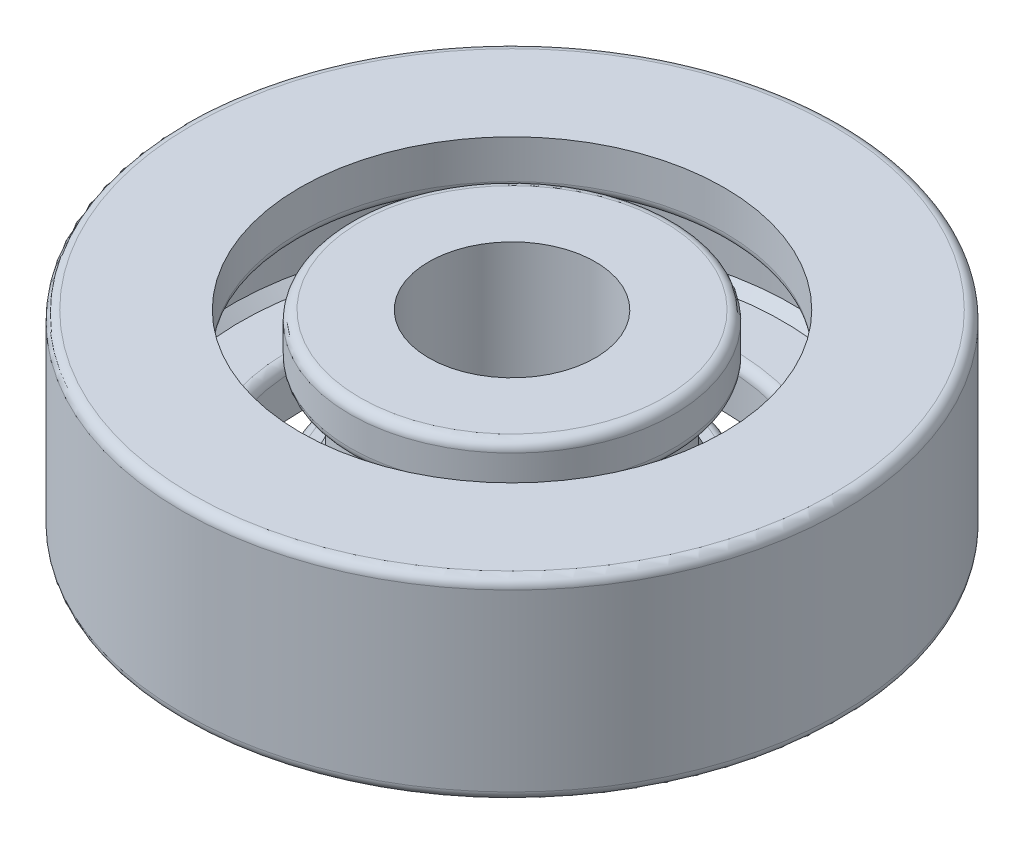
SolidWorks part; units mm, degrees
ref_plane "前视基准面" through (0, 0, 0) normal (0, 0, 1) x (1, 0, 0)
ref_plane "上视基准面" through (0, 0, 0) normal (0, 1, 0) x (1, 0, 0)
ref_plane "右视基准面" through (0, 0, 0) normal (1, 0, 0) x (0, 0, -1)
sketch "草图1" plane through (0, 0, 0) normal (0, 1, 0) x (1, 0, 0)
  circle A0 centre (0, 0) radius 57.8514
  circle A1 centre (0, 0) radius 43.6415
extrude "凸台-拉伸1" add sketch "草图1" along normal blind 20
sketch "草图2" plane through (0, 0, 0) normal (0, 1, 0) x (1, 0, 0)
  circle A0 centre (0, 0) radius 33.3134
  circle A1 centre (0, 0) radius 27.1507
extrude "凸台-拉伸2" add sketch "草图2" along normal blind 20 separate body
shell "抽壳1" thickness 10 removed face at (0, 20, 43.6415) outward yes
shell "抽壳2" thickness 10 removed face at (0, 20, 33.3134) outward yes
fillet "圆角1" radius 2 1 edges at (0, 0, 43.6415)
fillet "圆角2" radius 2 1 edges at (0, 20, 43.6415)
fillet "圆角3" radius 2 1 edges at (0, 30, 67.8514)
fillet "圆角4" radius 2 1 edges at (0, -10, 67.8514)
chamfer "倒角1" distance 2 angle 45 2 edges at (0, 20, 57.8514) (0, 0, 57.8514)
fillet "圆角5" radius 2 4 edges at (0, -10, 33.3134) (0, 0, 33.3134) (0, 20, 33.3134) (0, 30, 33.3134)
chamfer "倒角2" distance 2 angle 45 2 edges at (0, 20, 27.1507) (0, 0, 27.1507)
